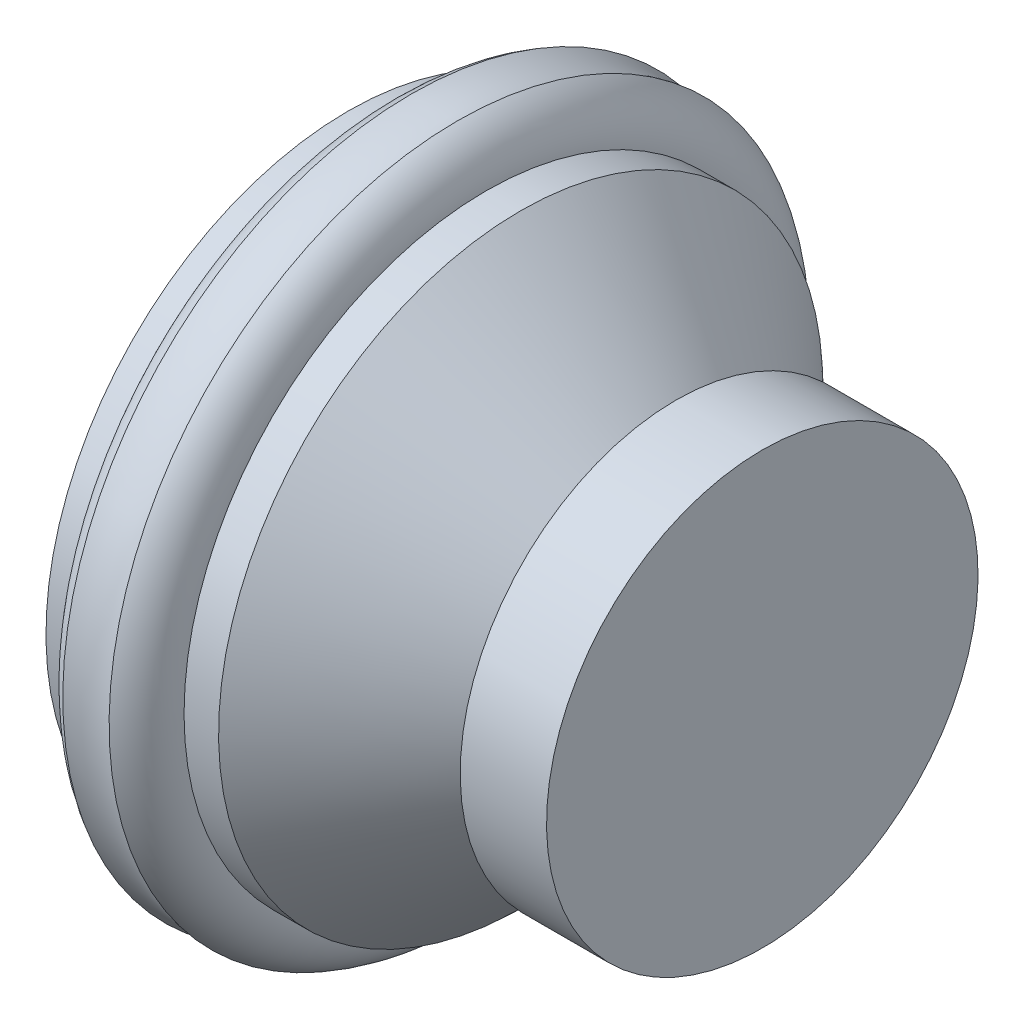
SolidWorks part; units mm, degrees
ref_plane "Front Plane" through (0, 0, 0) normal (0, 0, 1) x (1, 0, 0)
ref_plane "Top Plane" through (0, 0, 0) normal (0, 1, 0) x (1, 0, 0)
ref_plane "Right Plane" through (0, 0, 0) normal (1, 0, 0) x (0, 0, -1)
sketch "Sketch1" plane through (0, 0, 0) normal (0, 0, 1) x (1, 0, 0)
  line L0 (-119, 0) -> (-143, 0) construction
  line L1 (143, -52.5) -> (-143, -52.5) construction
  line L2 (143, -52.5) -> (143, 52.5) construction
  line L3 (143, 52.5) -> (-143, 52.5) construction
  line L4 (-143, -52.5) -> (-143, 52.5) construction
  line L5 (143, -52.5) -> (-143, 52.5) construction
  line L6 (143, 52.5) -> (-143, -52.5) construction
  line L7 (143, 52.5) -> (-119, 52.5) construction
  line L8 (143, 52.5) -> (143, -52.5) construction
  line L9 (143, -52.5) -> (-119, -52.5) construction
  line L10 (-119, 52.5) -> (-119, -52.5) construction
  line L11 (143, 52.5) -> (-119, -52.5) construction
  line L12 (143, -52.5) -> (-119, 52.5) construction
  line L13 (-119, -52.5) -> (-143, -52.5) construction
  line L14 (-119, -52.5) -> (-119, -47.5) construction
  line L15 (-119, -47.5) -> (-143, -47.5) construction
  line L16 (-143, -52.5) -> (-143, -47.5) construction
  line L17 (-119, -52.5) -> (-143, -47.5) construction
  line L18 (-119, -47.5) -> (-143, -52.5) construction
  line L19 (-119, 17.5) -> (-143, 17.5) construction
  line L20 (-119, 17.5) -> (-119, -17.5) construction
  line L21 (-119, -17.5) -> (-143, -17.5) construction
  line L22 (-143, 17.5) -> (-143, -17.5) construction
  line L23 (-119, 17.5) -> (-143, -17.5) construction
  line L24 (-119, -17.5) -> (-143, 17.5) construction
  line L25 (-119, 0) -> (-119, 12.5) construction
  line L26 (-133, 17.5) -> (-143, 17.5)
  line L27 (-119, 17.5) -> (-119, 0)
  line L28 (-119, 0) -> (-143, 0)
  line L29 (-143, 17.5) -> (-143, 0)
  line L30 (-119, 17.5) -> (-143, 0) construction
  line L31 (-119, 0) -> (-143, 17.5) construction
  line L32 (-143, 17.5) -> (-133, 17.5) construction
  line L33 (-119, 12.5) -> (-124, 12.5)
  line L34 (-119, 12.5) -> (-119, 0)
  line L35 (-119, 0) -> (-124, 0)
  line L36 (-124, 12.5) -> (-124, 9)
  line L37 (-119, 12.5) -> (-124, 0) construction
  line L38 (-119, 0) -> (-124, 12.5) construction
  line L39 (-124, 0) -> (-124, 9) construction
  line L40 (-124, 9) -> (-133, 17.5)
  line L41 (-124, 3.6458) -> (-124, 0)
  point P0 (0, 0)
  point P8 (12, 0)
  point P11 (-131, -50)
  point P16 (-131, 0)
  point P20 (-131, 8.75)
  point P23 (-121.5, 6.25)
  dimension "D1" = 262
  dimension "D2" = 286
  dimension "D3" = 105
  dimension "D4" = 5
  dimension "D5" = 35
  dimension "D6" = 35
  dimension "D7" = 12.5
  dimension "D8" = 5
  dimension "D9" = 10
  dimension "D10" = 9
revolve "Revolve2" add sketch "Sketch1" angle 360 about L28
sketch "Sketch2" plane through (0, 0, 0) normal (0, 0, 1) x (1, 0, 0)
  line L0 (-133, 17.5) -> (-143, 17.5) construction
  line L1 (-119, 0) -> (-143, 0) construction
  line L2 (-119, -12.5) -> (-119, 12.5) construction
  line L3 (-143, 17.5) -> (-143, -17.5) construction
  line L4 (-135, 17.5) -> (-141, 17.5)
  line L5 (-138, 17.5) -> (-138, 25) construction
  arc A0 (-135, 17.5) -> (-141, 17.5) centre (-138, 17.5) ccw
  arc A1 (-136.6585, 20.1833) -> (-139.3415, 20.1833) centre (-138, 25) cw
  dimension "D2" = 3
  dimension "D3" = 5
  dimension "D1" = 5
  dimension "D4" = 7.5
revolve "Revolve3" add sketch "Sketch2" angle 360 about L1 region at (-138, 18.6735, 0)
